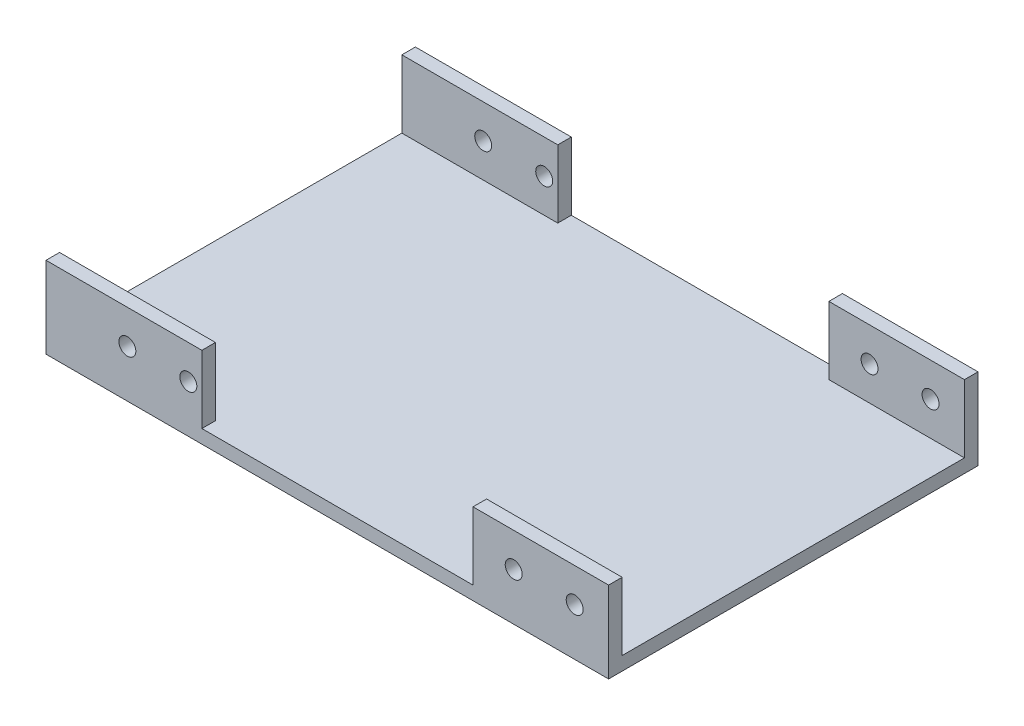
SolidWorks part; units mm, degrees
ref_plane "Front Plane" through (0, 0, 0) normal (0, 0, 1) x (1, 0, 0)
ref_plane "Top Plane" through (0, 0, 0) normal (0, 1, 0) x (1, 0, 0)
ref_plane "Right Plane" through (0, 0, 0) normal (1, 0, 0) x (0, 0, -1)
sketch "Sketch1" plane through (0, 0, 0) normal (0, 1, 0) x (1, 0, 0)
  line L1 (-61.9985, 29.194) -> (21.0015, 29.194)
  line L2 (-61.9985, 29.194) -> (-61.9985, -25.306)
  line L3 (-61.9985, -25.306) -> (21.0015, -25.306)
  line L4 (21.0015, 29.194) -> (21.0015, -25.306)
  dimension "D1" = 83
  dimension "D2" = 54.5
extrude "Boss-Extrude1" add sketch "Sketch1" along normal blind 2
sketch "Sketch2" plane through (0, 2, 0) normal (0, 1, 0) x (1, 0, 0)
  line L0 (21.0015, 29.194) -> (-61.9985, 29.194) construction
  line L1 (1.0015, 29.194) -> (21.0015, 29.194)
  line L2 (1.0015, 29.194) -> (1.0015, 27.194)
  line L3 (1.0015, 27.194) -> (21.0015, 27.194)
  line L4 (21.0015, 29.194) -> (21.0015, 27.194)
  line L5 (1.0015, -23.306) -> (21.0015, -23.306)
  line L6 (1.0015, -23.306) -> (1.0015, -25.306)
  line L7 (1.0015, -25.306) -> (21.0015, -25.306)
  line L8 (21.0015, -23.306) -> (21.0015, -25.306)
  line L9 (-61.9985, -25.306) -> (21.0015, -25.306) construction
  line L10 (21.0015, -25.306) -> (21.0015, 29.194) construction
  line L11 (-61.9985, 29.194) -> (-61.9985, -25.306) construction
  line L16 (-61.9985, 29.194) -> (-38.9985, 29.194)
  line L17 (-61.9985, 29.194) -> (-61.9985, 27.194)
  line L18 (-61.9985, 27.194) -> (-38.9985, 27.194)
  line L19 (-38.9985, 29.194) -> (-38.9985, 27.194)
  line L20 (-61.9985, -23.306) -> (-38.9985, -23.306)
  line L21 (-61.9985, -23.306) -> (-61.9985, -25.306)
  line L22 (-61.9985, -25.306) -> (-38.9985, -25.306)
  line L23 (-38.9985, -23.306) -> (-38.9985, -25.306)
  dimension "D1" = 20
  dimension "D2" = 2
  dimension "D3" = 20
  dimension "D4" = 2
  dimension "D5" = 0
  dimension "D6" = 0
  dimension "D7" = 0
  dimension "D8" = 0
  dimension "D9" = 2
  dimension "D10" = 2
  dimension "D11" = 60
  dimension "D12" = 60
  dimension "D13" = 0
  dimension "D14" = 0
  dimension "D15" = 0
  dimension "D16" = 0
extrude "Boss-Extrude2" add sketch "Sketch2" along normal blind 10
sketch "Sketch3" plane through (0, 0, 25.306) normal (0, 0, 1) x (1, 0, 0)
  line L1 (21.0015, 12) -> (21.0015, 0) construction
  line L2 (-38.9985, 2) -> (1.0015, 2) construction
  circle A0 centre (16.0015, 7) radius 1.25
  circle A1 centre (7.0015, 7) radius 1.25
  circle A2 centre (-40.9985, 7) radius 1.25
  circle A3 centre (-49.9985, 7) radius 1.25
  dimension "D1" = 2.5
  dimension "D2" = 2.5
  dimension "D3" = 2.5
  dimension "D4" = 2.5
  dimension "D5" = 5
  dimension "D6" = 5
  dimension "D7" = 9
  dimension "D8" = 5
  dimension "D9" = 5
  dimension "D10" = 5
  dimension "D11" = 9
  dimension "D12" = 48
extrude "Cut-Extrude1" cut sketch "Sketch3" against normal through all
